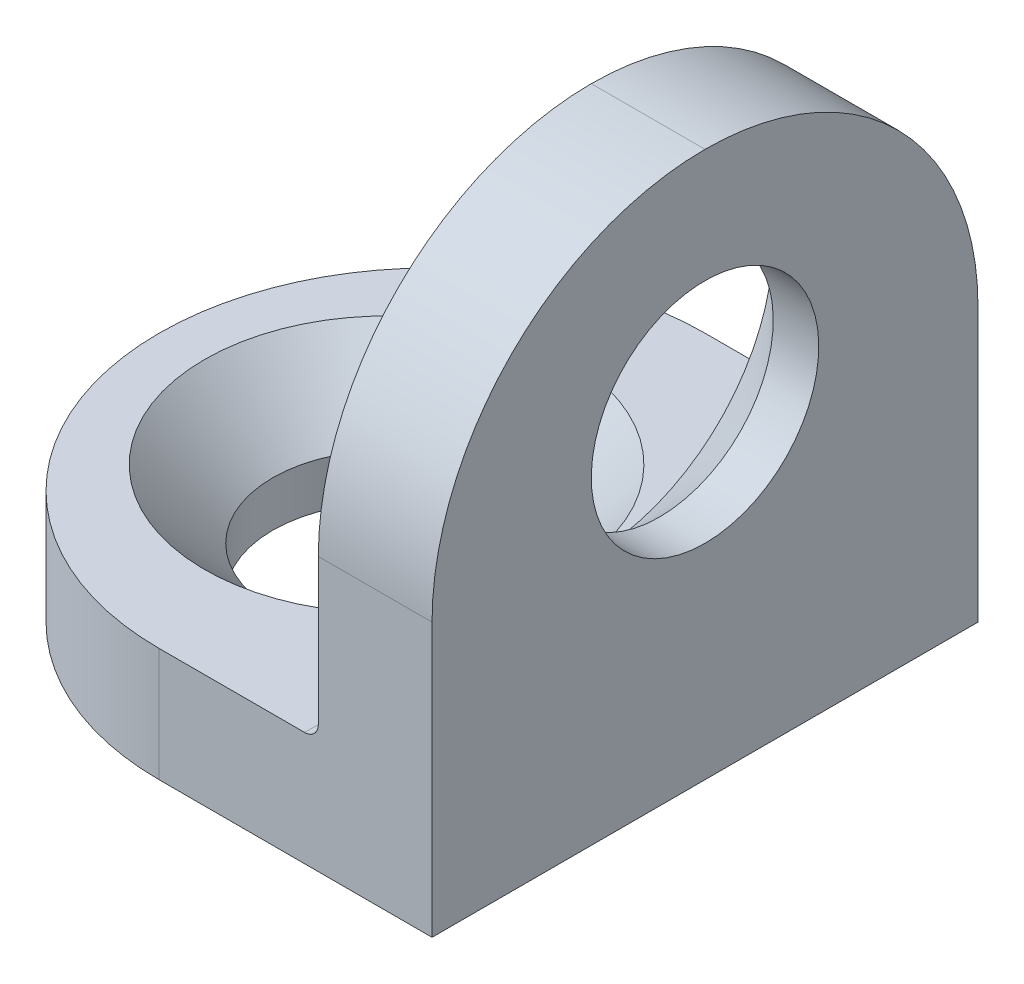
SolidWorks part; units mm, degrees
ref_plane "Plano frontal" through (0, 0, 0) normal (0, 0, 1) x (1, 0, 0)
ref_plane "Plano superior" through (0, 0, 0) normal (0, 1, 0) x (1, 0, 0)
ref_plane "Plano direito" through (0, 0, 0) normal (1, 0, 0) x (0, 0, -1)
sketch "Esboço2" plane through (0, 0, 0) normal (0, 0, 1) x (1, 0, 0)
  line L0 (0, 0) -> (0, -2.5)
  line L1 (0, -2.5) -> (12, -2.5)
  line L2 (12, -2.5) -> (12, 9.5)
  line L3 (12, 9.5) -> (9.5, 9.5)
  line L4 (9.5, 9.5) -> (9.5, 0)
  line L5 (9.5, 0) -> (0, 0)
  dimension "D1" = 12
  dimension "D2" = 2.5
extrude "Ressalto-extrusão1" add sketch "Esboço2" against normal blind 12
fillet "Filete1" radius 6 2 edges at (10.75, 9.5, 0) (10.75, 9.5, -12)
fillet "Filete2" radius 6 2 edges at (0, -1.25, 0) (0, -1.25, -12)
sketch "Esboço3" plane through (0, 0, 0) normal (0, 1, 0) x (1, 0, 0)
  circle A0 centre (5, 6) radius 2.5
  dimension "D1" = 5
  dimension "D2" = 5
extrude "Corte-extrusão1" cut sketch "Esboço3" against normal through all
fillet "Filete3" radius 0.3 1 edges at (9.5, 0, -6)
sketch "Esboço4" plane through (9.5, 0, 0) normal (-1, 0, 0) x (0, 0, 1)
  circle A0 centre (-6, 4.5) radius 2.5
  dimension "D1" = 5
  dimension "D2" = 5
extrude "Corte-extrusão2" cut sketch "Esboço4" against normal through all
chamfer "Chanfro2" distance 1.5 angle 45 2 edges at (9.5, 2, -6) (2.5, 0, -6)
